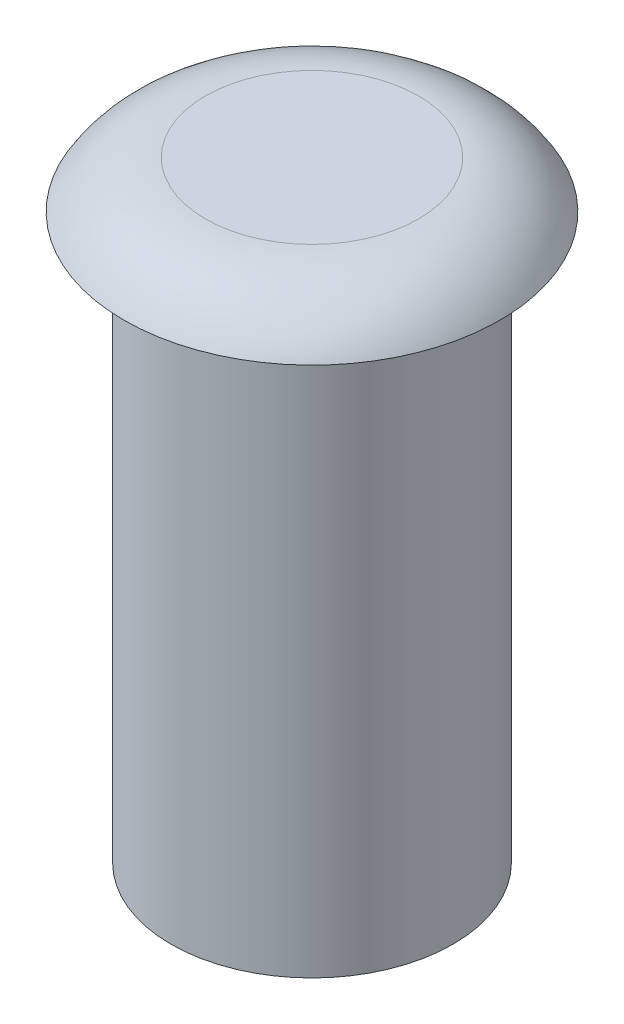
SolidWorks part; units mm, degrees
ref_plane "Front Plane" through (0, 0, 0) normal (0, 0, 1) x (1, 0, 0)
ref_plane "Top Plane" through (0, 0, 0) normal (0, 1, 0) x (1, 0, 0)
ref_plane "Right Plane" through (0, 0, 0) normal (1, 0, 0) x (0, 0, -1)
sketch "Sketch1" plane through (0, 0, 0) normal (0, 1, 0) x (1, 0, 0)
  circle A0 centre (0, 0) radius 1.5
extrude "Boss-Extrude1" add sketch "Sketch1" along normal blind 6
sketch "Sketch2" plane through (0, 6, 0) normal (0, 1, 0) x (1, 0, 0)
  circle A0 centre (0, 0) radius 2
extrude "Boss-Extrude2" add sketch "Sketch2" along normal blind 0.5
fillet "Fillet2" radius 1 1 edges at (0, 6.5, 2)
